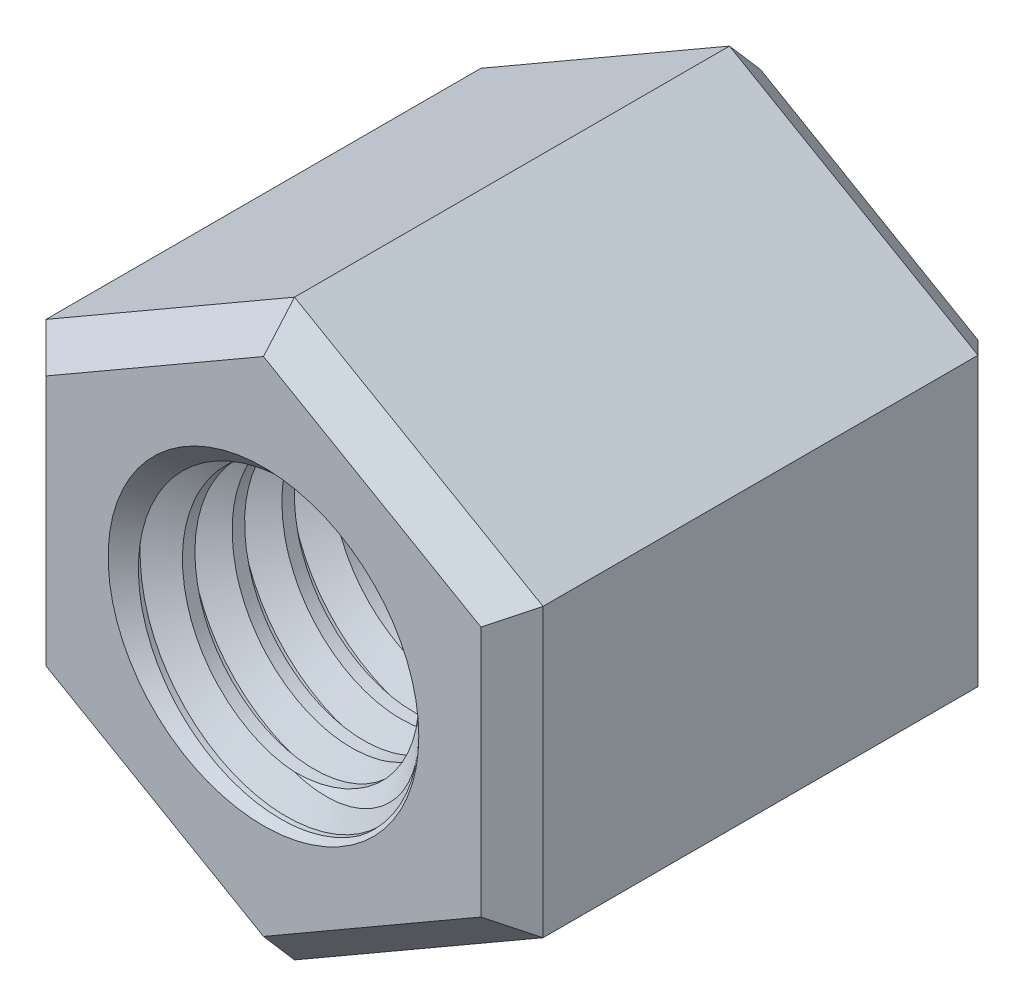
SolidWorks part; units mm, degrees
ref_plane "Front Plane" through (0, 0, 0) normal (0, 0, 1) x (1, 0, 0)
ref_plane "Top Plane" through (0, 0, 0) normal (0, 1, 0) x (1, 0, 0)
ref_plane "Right Plane" through (0, 0, 0) normal (1, 0, 0) x (0, 0, -1)
sketch "Sketch1" plane through (0, 0, 0) normal (0, 0, 1) x (1, 0, 0)
  line L1 (0, -4.6188) -> (4, -2.3094)
  line L2 (4, -2.3094) -> (4, 2.3094)
  line L3 (4, 2.3094) -> (0, 4.6188)
  line L4 (0, 4.6188) -> (-4, 2.3094)
  line L5 (-4, 2.3094) -> (-4, -2.3094)
  line L6 (-4, -2.3094) -> (0, -4.6188)
  circle A0 centre (0, 0) radius 4 construction
  point P1 (0, 0)
  dimension "D1" = 8
extrude "Boss-Extrude1" add sketch "Sketch1" along normal blind 8
chamfer "Chamfer1" distance 0.5 angle 45 12 edges at (4, 0, 0) (2, -3.4641, 0) (-2, -3.4641, 0) (-4, 0, 0) (-2, 3.4641, 0) (2, 3.4641, 0) (-2, 3.4641, 8) (-4, 0, 8) (-2, -3.4641, 8) (2, -3.4641, 8) (4, 0, 8) (2, 3.4641, 8)
sketch "Sketch2" plane through (0, 0, 8) normal (0, 0, 1) x (1, 0, 0)
  circle A0 centre (0, 0) radius 2
  dimension "D1" = 4
extrude "Cut-Extrude1" cut sketch "Sketch2" against normal blind 8
chamfer "Chamfer2" distance 0.5 angle 45 2 edges at (2, 0, 0) (2, 0, 8)
thread "Thread1" pitch 0.8 method cut profile "Thread Profile1" start angle 0, offset 2, length 10, pitch 0.8, diameter 4
ref_plane "Plane1" through (-2, 0, 9.5) normal (0, -1, 0) x (-1, 0, 0)
sketch "Thread Profile1" plane through (-2, 0, 9.5) normal (0, -1, 0) x (-1, 0, 0)
  line L0 (0, 0) -> (0, 0.8) construction
  line L1 (0, 0) -> (0.433, 0.25)
  line L2 (0.433, 0.25) -> (0.433, 0.35)
  line L3 (0.433, 0.35) -> (0, 0.6)
  line L4 (0.433, 0.3) -> (0, 0.3) construction
  line L11 (0, 0) -> (0, 0.6)
  point P2 (0, 0)
  dimension "Pitch" = 0.8
  dimension "Profile_Angle" = 60
  dimension "Profile_Land" = 0.1
  dimension "Profile_Height" = 0.433
